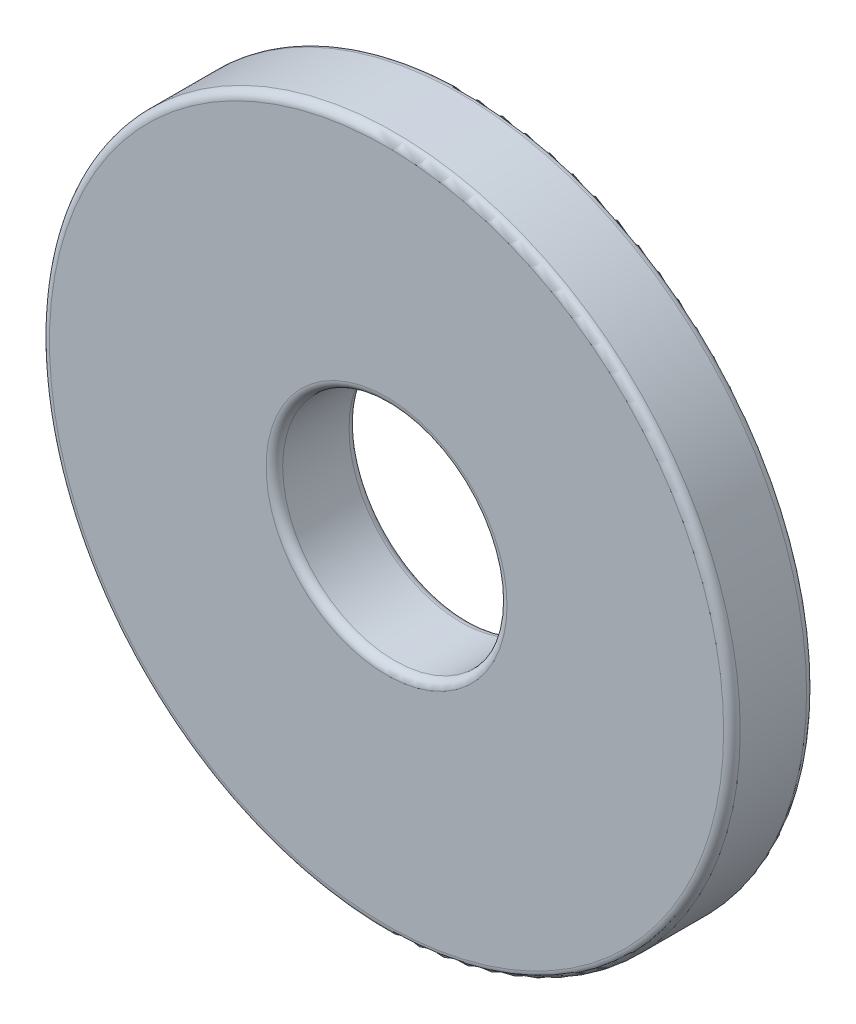
SolidWorks part; units mm, degrees
material "AISI 304"
ref_plane "Front Plane" through (0, 0, 0) normal (0, 0, 1) x (1, 0, 0)
ref_plane "Top Plane" through (0, 0, 0) normal (0, 1, 0) x (1, 0, 0)
ref_plane "Right Plane" through (0, 0, 0) normal (1, 0, 0) x (0, 0, -1)
sketch "Sketch1" plane through (0, 0, 0) normal (0, 0, 1) x (1, 0, 0)
  circle A0 centre (0, 0) radius 2.5781
  circle A1 centre (0, 0) radius 7.9375
  point P4 (0, 7.9375)
  point P5 (0, 2.5781)
  point P6 (0, -2.5781)
  point P7 (2.5781, 0)
  point P8 (-2.5781, 0)
  dimension "OD" = 15.875
  dimension "ID" = 5.1562
sketch "Sketch2" plane through (0, 0, 0) normal (1, 0, 0) x (0, 0, -1)
  line L1 (-0.9525, 7.9375) -> (0.9525, 7.9375)
  line L2 (-0.9525, 7.9375) -> (-0.9525, -7.9375)
  line L3 (-0.9525, -7.9375) -> (0.9525, -7.9375)
  line L4 (0.9525, 7.9375) -> (0.9525, -7.9375)
  point P4 (0, 7.9375)
  point P5 (0.9525, 0)
  dimension "Thickness" = 1.905
sketch "Sketch3" plane through (0, 0, 0) normal (0, 0, 1) x (1, 0, 0)
  circle A0 centre (0, 0) radius 2.5781 construction
  circle A1 centre (0, 0) radius 7.9375 construction
  circle A2 centre (0, 0) radius 2.5781
  circle A3 centre (0, 0) radius 7.9375
extrude "Boss-Extrude1" add sketch "Sketch3" against normal up to vertex (0.9525 mm away) from vertex up to point (0, 7.9375, -0.9525) starting at point (0, 7.9375, 0.9525)
fillet "Fillet1" radius 0.1905 4 edges at (2.5781, 0, 0.9525) (2.5781, 0, -0.9525) (7.9375, 0, 0.9525) (7.9375, 0, -0.9525)
equation "\"D1@Fillet1\"=\"Thickness@Sketch2\"*.1"
